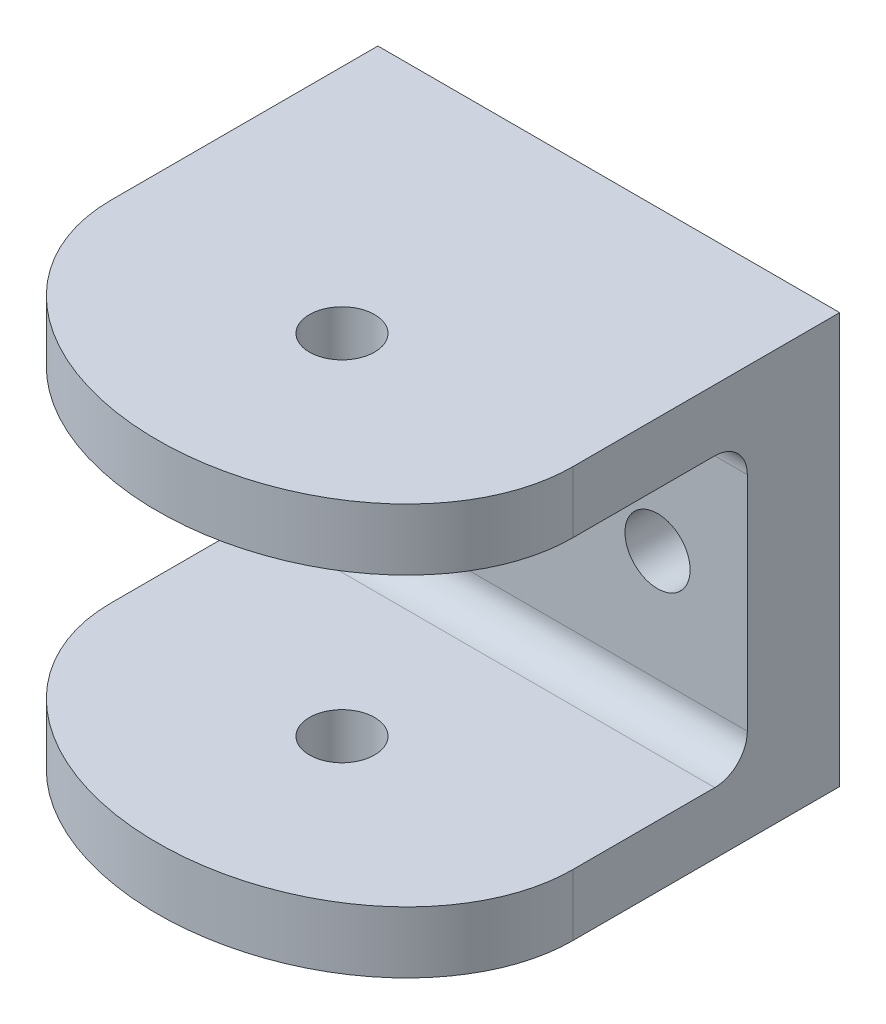
SolidWorks part; units mm, degrees
ref_plane "Front Plane" through (0, 0, 0) normal (0, 0, 1) x (1, 0, 0)
ref_plane "Top Plane" through (0, 0, 0) normal (0, 1, 0) x (1, 0, 0)
ref_plane "Right Plane" through (0, 0, 0) normal (1, 0, 0) x (0, 0, -1)
sketch "Sketch1" plane through (0, 0, 0) normal (0, 0, 1) x (1, 0, 0)
  line L0 (0, 0) -> (-13.75, 0) construction
  line L1 (-22.5, -20) -> (22.5, -20)
  line L2 (-22.5, -20) -> (-22.5, 20)
  line L3 (-22.5, 20) -> (22.5, 20)
  line L4 (22.5, -20) -> (22.5, 20)
  line L5 (-22.5, -20) -> (22.5, 20) construction
  line L6 (-22.5, 20) -> (22.5, -20) construction
  line L7 (0, 0) -> (13.75, 0) construction
  circle A0 centre (13.75, 0) radius 3.175
  circle A1 centre (-13.75, 0) radius 3.175
  point P0 (0, 0)
  dimension "D4" = 6.35
  dimension "D1" = 45
  dimension "D2" = 40
  dimension "D3" = 27.5
extrude "Boss-Extrude1" add sketch "Sketch1" along normal blind 9
sketch "Sketch2" plane through (0, 0, 9) normal (0, 0, 1) x (1, 0, 0)
  line L1 (-22.5, 20) -> (22.5, 20)
  line L2 (-22.5, 20) -> (-22.5, 14)
  line L3 (-22.5, 14) -> (22.5, 14)
  line L4 (22.5, -20) -> (22.5, 20)
  line L5 (22.5, 20) -> (-22.5, 20)
  line L6 (-22.5, 20) -> (-22.5, -20)
  line L7 (-22.5, -20) -> (22.5, -20)
  line L8 (22.5, -20) -> (22.5, 20) construction
  line L9 (22.5, 20) -> (-22.5, 20) construction
  line L10 (-22.5, 20) -> (-22.5, -20) construction
  line L11 (-22.5, -20) -> (22.5, -20) construction
  line L12 (22.5, 20) -> (22.5, 14)
  line L13 (22.5, -20) -> (-22.5, -20)
  line L14 (22.5, -20) -> (22.5, -14)
  line L15 (22.5, -14) -> (-22.5, -14)
  line L16 (-22.5, -20) -> (-22.5, -14)
  dimension "D2" = 6
  dimension "D3" = 6
  dimension "D1" = 0
extrude "Boss-Extrude2" add sketch "Sketch2" along normal blind 35
fillet "Fillet1" radius 3.175 2 edges at (0, 14, 9) (0, -14, 9)
sketch "Sketch3" plane through (0, 20, 0) normal (0, 1, 0) x (1, 0, 0)
  line L0 (22.5, -9) -> (-22.5, -9) construction
  line L1 (22.5, -9) -> (-22.5, -9) construction
  line L2 (22.5, -44) -> (22.5, 0) construction
  line L3 (22.5, -44) -> (22.5, -26)
  line L4 (-22.5, -44) -> (-22.5, 0) construction
  line L6 (-22.5, -44) -> (-22.5, -26)
  line L7 (22.5, -44) -> (-22.5, -44)
  line L8 (22.5, 0) -> (-22.5, 0) construction
  circle A0 centre (0, -26) radius 3.175
  ellipse E0 centre (0, -26) end of major axis (-22.5, -26) minor radius 18 (-22.5, -26) -> (7.3951, -9) ccw
  point P4 (0, -9)
  point P7 (0, 0)
  point P13 (0, 0)
  line M6 (-22.5, 0) -> (-22.5, -44)
  line M7 (-22.5, -44) -> (22.5, -44)
  line M8 (22.5, -44) -> (22.5, 0)
  dimension "D1" = 6.35
  dimension "D2" = 26
  dimension "D3" = 22.5
  dimension "D4" = 0
  dimension "D5" = 18
extrude "Cut-Extrude1" cut sketch "Sketch3" against normal through all contours M6 M7 | L7 M8 | A0 region at (17.4767, 20, 39.9774) region at (-17.4742, 20, 39.9794) region at (0, 20, 26)
ref_point "Point4"
ref_point "Point6"
ref_point "Point8"
ref_point "Point12"
sketch "Sketch4" plane through (0, 0, 0) normal (0, 1, 0) x (1, 0, 0)
  point P0 (0, -26)
